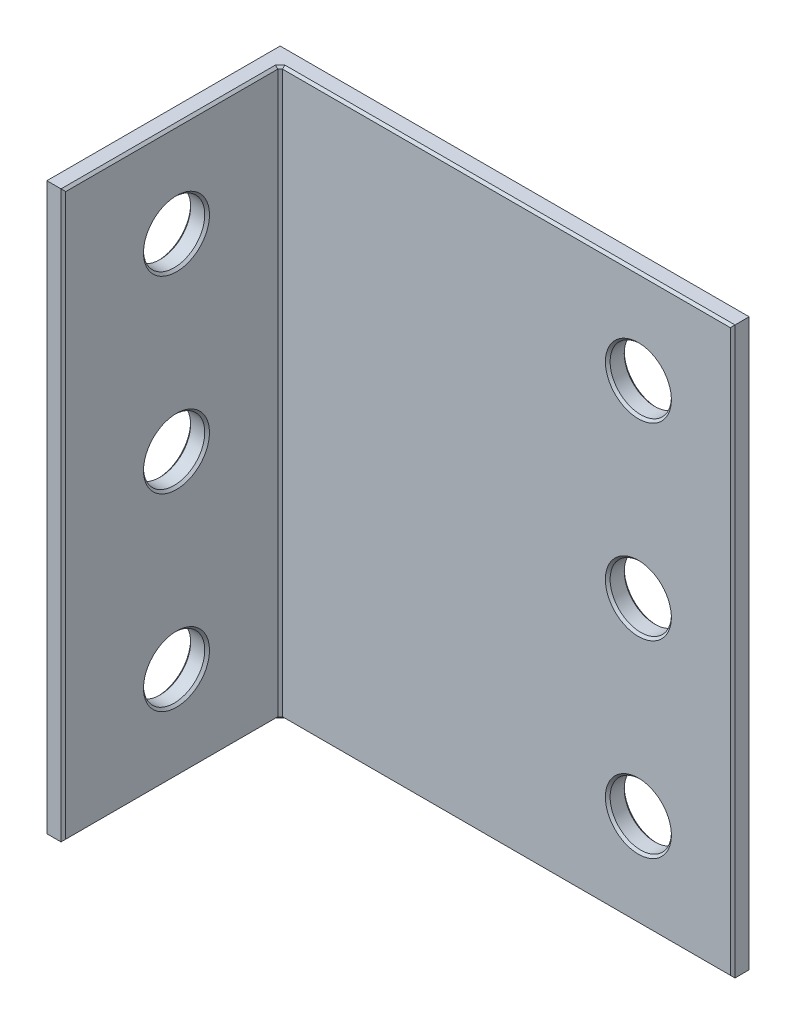
SolidWorks part; units mm, degrees
ref_plane "前视" through (0, 0, 0) normal (0, 0, 1) x (1, 0, 0)
ref_plane "上视" through (0, 0, 0) normal (0, 1, 0) x (1, 0, 0)
ref_plane "右视" through (0, 0, 0) normal (1, 0, 0) x (0, 0, -1)
sketch "草图1" plane through (0, 0, 0) normal (0, 0, 1) x (1, 0, 0)
  line L0 (160, 281.9635) -> (160, -120.4694) construction
  line L1 (0, 0) -> (200, 0)
  line L2 (0, 0) -> (0, 240)
  line L3 (0, 240) -> (200, 240)
  line L4 (200, 0) -> (200, 240)
  circle A0 centre (160, 40) radius 13
  circle A1 centre (160, 120) radius 13
  circle A2 centre (160, 200) radius 13
  dimension "D7" = 26
  dimension "D1" = 240
  dimension "D2" = 200
  dimension "D3" = 160
  dimension "D4" = 40
  dimension "D5" = 80
  dimension "D6" = 80
extrude "基体-拉伸" add sketch "草图1" along normal blind 8
sketch "草图2" plane through (0, 0, 8) normal (0, 0, 1) x (1, 0, 0)
  line L1 (0, 240) -> (8, 240)
  line L2 (0, 240) -> (0, 0)
  line L3 (0, 0) -> (8, 0)
  line L4 (8, 240) -> (8, 0)
  dimension "D1" = 8
extrude "凸台-拉伸1" add sketch "草图2" along normal blind 92
sketch "草图3" plane through (0, 0, 0) normal (-1, 0, 0) x (0, 0, 1)
  line L0 (52, 245.7913) -> (52, 32.4579) construction
  line L1 (0, 240) -> (0, 0) construction
  line L2 (100, 240) -> (0, 240) construction
  circle A0 centre (52, 200) radius 13
  circle A1 centre (52, 120) radius 13
  circle A2 centre (52, 40) radius 13
  dimension "D5" = 26
  dimension "D1" = 52
  dimension "D2" = 40
  dimension "D3" = 80
  dimension "D4" = 80
extrude "切除-拉伸1" cut sketch "草图3" against normal through all
chamfer "倒角1" distance 1 angle 45 26 edges at (173, 200, 0) (173, 40, 0) (173, 120, 0) (173, 120, 8) (173, 40, 8) (173, 200, 8) (100, 0, 0) (200, 120, 0) (100, 240, 0) (0, 240, 50) (0, 120, 100) (0, 0, 50) (0, 120, 0) (0, 200, 65) (0, 120, 65) (0, 40, 65) (104, 240, 8) (200, 120, 8) (104, 0, 8) (8, 0, 54) (8, 120, 100) (8, 240, 54) (8, 120, 8) (8, 187, 52) (8, 107, 52) (8, 27, 52)
sketch "草图4" plane through (8, 0, 0) normal (1, 0, 0) x (0, 0, -1)
